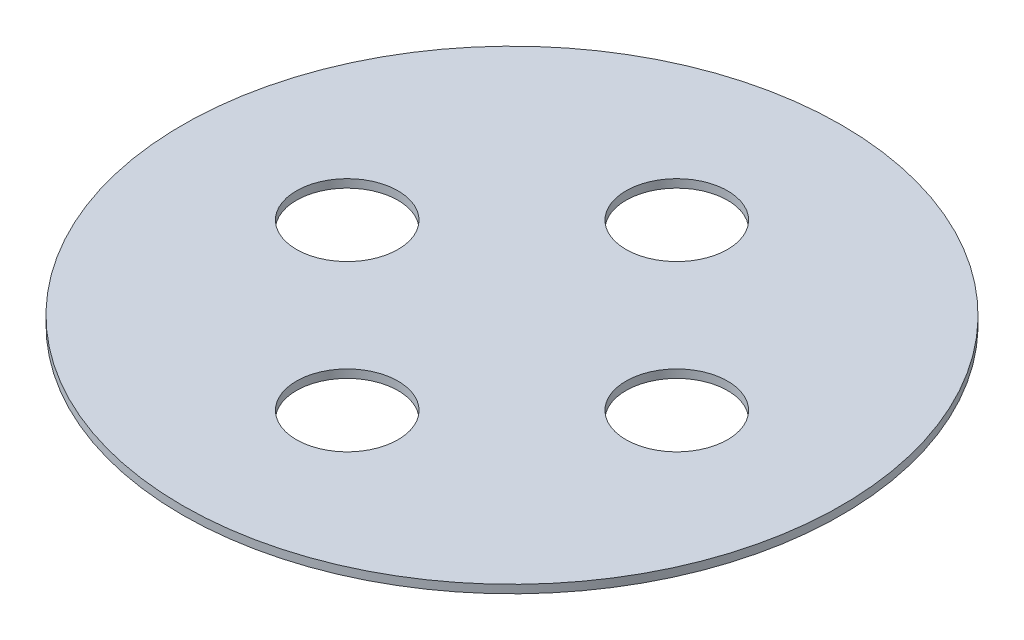
SolidWorks part; units mm, degrees
ref_plane "前视基准面" through (0, 0, 0) normal (0, 0, 1) x (1, 0, 0)
ref_plane "上视基准面" through (0, 0, 0) normal (0, 1, 0) x (1, 0, 0)
ref_plane "右视基准面" through (0, 0, 0) normal (1, 0, 0) x (0, 0, -1)
sketch "草图1" plane through (0, 0, 0) normal (0, 1, 0) x (1, 0, 0)
  line L0 (-1000, 0) -> (49000, 0) construction
  circle A0 centre (0, 0) radius 9.9
  circle A1 centre (6, 0) radius 1.85
  circle A2 centre (0, -6) radius 1.85
  circle A3 centre (-6, 0) radius 1.85
  circle A4 centre (0, 6) radius 1.85
  point P16 (0, 0)
  dimension "D1" = 19.8
  dimension "D2" = 3.7
  dimension "D3" = 6
  dimension "D4" = 4
extrude "凸台-拉伸1" add sketch "草图1" along normal blind 7
sketch "草图2" plane through (0, 7, 0) normal (0, 1, 0) x (1, 0, 0)
  circle A0 centre (0, 0) radius 12.5
  circle A1 centre (-6, 0) radius 1.85 construction
  circle A2 centre (0, -6) radius 1.85 construction
  circle A3 centre (6, 0) radius 1.85 construction
  circle A4 centre (0, 6) radius 1.85 construction
  circle A5 centre (-6, 0) radius 1.85
  circle A6 centre (0, -6) radius 1.85
  circle A7 centre (6, 0) radius 1.85
  circle A8 centre (0, 6) radius 1.85
  dimension "D1" = 25
extrude "凸台-拉伸2" add sketch "草图2" along normal blind 2.5
sketch "草图3" plane through (0, 9.5, 0) normal (0, 1, 0) x (1, 0, 0)
  line L0 (-1000, 0) -> (49000, 0) construction
  line L1 (33, -7.5) -> (10, -7.5)
  line L2 (33, 7.5) -> (10, 7.5)
  circle A0 centre (0, -6) radius 1.85 construction
  circle A1 centre (-6, 0) radius 1.85 construction
  circle A2 centre (0, 6) radius 1.85 construction
  circle A3 centre (6, 0) radius 1.85 construction
  circle A4 centre (0, 0) radius 12.5 construction
  circle A5 centre (0, -6) radius 1.85
  circle A6 centre (-6, 0) radius 1.85
  circle A7 centre (0, 6) radius 1.85
  circle A8 centre (6, 0) radius 1.85
  circle A9 centre (0, 0) radius 12.5
  circle A10 centre (33, 0) radius 4.35
  circle A11 centre (6, 0) radius 3.75
  circle A12 centre (0, -6) radius 3.75
  circle A13 centre (-6, 0) radius 3.75
  circle A14 centre (0, 6) radius 3.75
  circle A15 centre (33, 0) radius 7.5
  point P29 (0, 0)
  circle M13 centre (0, 0) radius 12.5
  dimension "D1" = 8.7
  dimension "D2" = 7.5
  dimension "D4" = 33
  dimension "D5" = 15
  dimension "D3" = 4
extrude "凸台-拉伸3" add sketch "草图3" along normal blind 6.3 contours L0 A9 A11 A13 A12 M13 | L0 A13 A11 A9 A14 M13 | A9 L0 A15 L2 | L0 L1 A15 M13 | L0 A15 A10 | A15 L0 A10 region at (-6, 9.5, -4.0295) region at (0, 9.5, 0.2795) region at (19.4799, 9.5, -4.0658) region at (19.4799, 9.5, 4.0658) region at (27.8153, 9.5, -5.1847) region at (27.075, 9.5, 0.1677)
chamfer "倒角1" distance 2 angle 45 4 edges at (0, 9.5, 9.75) (-6, 9.5, 3.75) (0, 9.5, -2.25) (6, 9.5, 3.75)
sketch "草图4" plane through (0, 15.8, 0) normal (0, 1, 0) x (1, 0, 0)
  circle A0 centre (0, 0) radius 41.5
  dimension "D1" = 83
extrude "切除-拉伸1" cut sketch "草图4" against normal offset from surface (15.5 mm away) 0.3 up to face at (0, 0, 9.9)
sketch "草图5" plane through (0, 0.3, 0) normal (0, 1, 0) x (1, 0, 0)
  circle A0 centre (0, 0) radius 12
  circle M6 centre (0, 0) radius 9.9
  dimension "D1" = 24
extrude "凸台-拉伸4" add sketch "草图5" against normal blind 0.3 contours A0 M6 region at (-11.6606, 0.3, 0)
